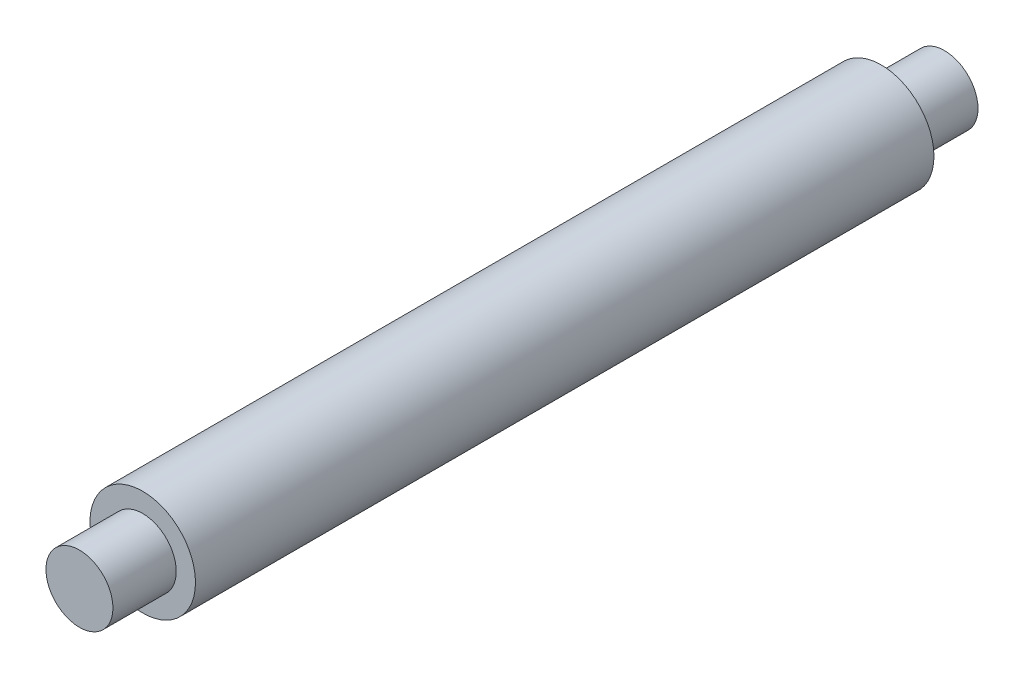
SolidWorks part; units mm, degrees
ref_plane "Front Plane" through (0, 0, 0) normal (0, 0, 1) x (1, 0, 0)
ref_plane "Top Plane" through (0, 0, 0) normal (0, 1, 0) x (1, 0, 0)
ref_plane "Right Plane" through (0, 0, 0) normal (1, 0, 0) x (0, 0, -1)
sketch "Sketch1" plane through (0, 0, 0) normal (0, 0, 1) x (1, 0, 0)
  circle A0 centre (0, 0) radius 3.175
  dimension "D1" = 6.35
extrude "Boss-Extrude1" add sketch "Sketch1" along normal mid plane 82
sketch "Sketch2" plane through (0, 0, 0) normal (0, 0, 1) x (1, 0, 0)
  circle A0 centre (0, 0) radius 5
  dimension "D1" = 10
extrude "Boss-Extrude2" add sketch "Sketch2" along normal mid plane 70 separate body
